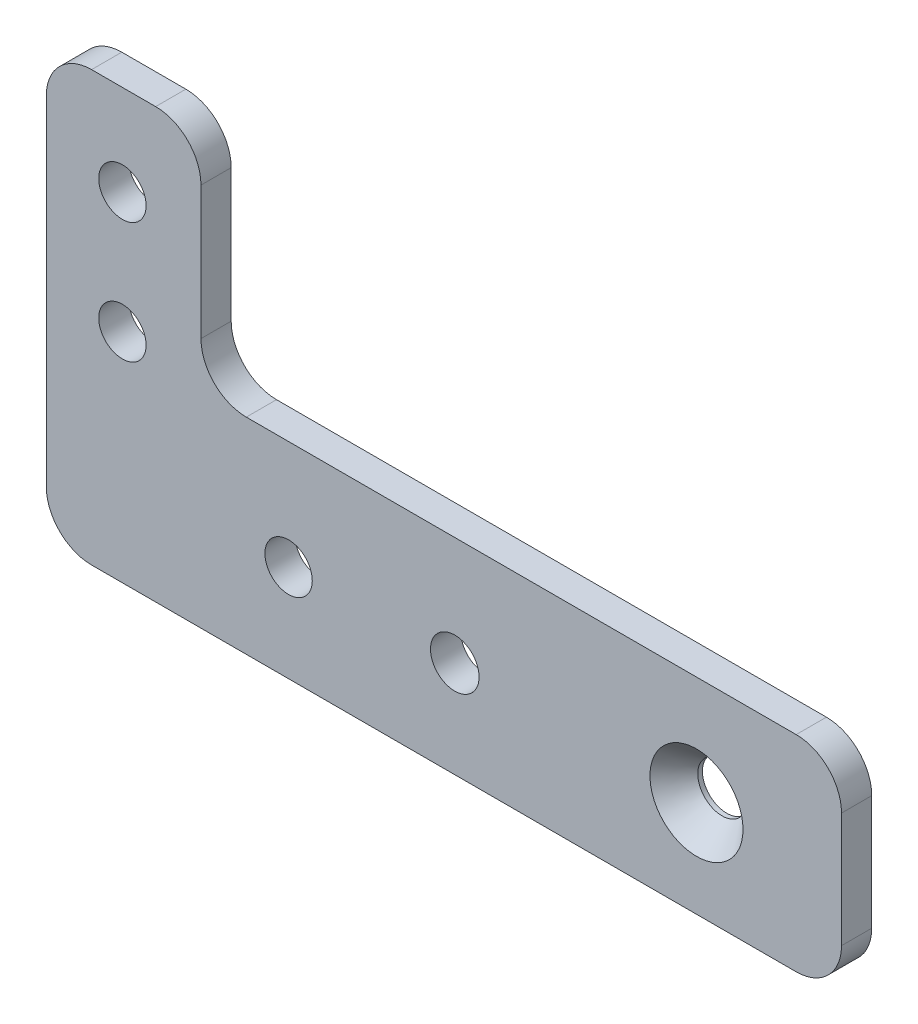
SolidWorks part; units mm, degrees
material "6061-T6 (SS)"
ref_plane "Front Plane" through (0, 0, 0) normal (0, 0, 1) x (1, 0, 0)
ref_plane "Top Plane" through (0, 0, 0) normal (0, 1, 0) x (1, 0, 0)
ref_plane "Right Plane" through (0, 0, 0) normal (1, 0, 0) x (0, 0, -1)
sketch "Sketch1" plane through (0, 0, 0) normal (0, 0, 1) x (1, 0, 0)
  line L0 (-21.59, 23.8125) -> (-37.846, 23.8125) construction
  line L1 (-45.72, -23.8125) -> (45.72, -23.8125)
  line L2 (-45.72, -23.8125) -> (-45.72, 23.8125)
  line L3 (-45.72, 23.8125) -> (45.72, 23.8125)
  line L4 (45.72, -23.8125) -> (45.72, 23.8125)
  line L5 (-45.72, -23.8125) -> (45.72, 23.8125) construction
  line L6 (-45.72, 23.8125) -> (45.72, -23.8125) construction
  line L7 (45.72, 23.8125) -> (-21.59, 23.8125)
  line L8 (45.72, 23.8125) -> (45.72, 0.3175)
  line L9 (45.72, 0.3175) -> (-21.59, 0.3175)
  line L10 (-21.59, 23.8125) -> (-21.59, 0.3175)
  line L11 (-45.72, -23.8125) -> (-37.846, -23.8125)
  line L12 (-45.72, -23.8125) -> (-45.72, 23.8125)
  line L13 (-45.72, 23.8125) -> (-37.846, 23.8125)
  line L14 (-37.846, -23.8125) -> (-37.846, 23.8125)
  line L15 (-37.846, -23.8125) -> (45.72, -23.8125)
  line L16 (-37.846, -23.8125) -> (-37.846, -21.2725)
  line L17 (-37.846, -21.2725) -> (45.72, -21.2725)
  line L18 (45.72, -23.8125) -> (45.72, -21.2725)
  line L19 (-21.59, 23.8125) -> (-37.846, 23.8125) construction
  line L20 (-29.845, 23.8125) -> (-29.845, -21.2725) construction
  circle A0 centre (-29.845, -11.1125) radius 2.4892
  circle A1 centre (-29.845, 1.5875) radius 2.4892
  circle A2 centre (-29.845, 14.2875) radius 2.4892
  circle A4 centre (-12.3825, -11.1125) radius 2.4892
  circle A5 centre (5.08, -11.1125) radius 2.5527
  circle A7 centre (30.48, -11.1125) radius 2.5527
  point P0 (0, 0)
  dimension "D7" = 17.4625
  dimension "D18" = 5.1054
  dimension "D19" = 4.9784
  dimension "D13" = 25.4
  dimension "D8" = 50.8
  dimension "D1" = 91.44
  dimension "D2" = 9.525
  dimension "D3" = 24.13
  dimension "D4" = 24.13
  dimension "D5" = 7.874
  dimension "D6" = 47.625
  dimension "D9" = 12.7
  dimension "D10" = 12.7
  dimension "D11" = 12.7
  dimension "D12" = 15.875
  dimension "D16" = 2.54
extrude "Boss-Extrude1" add sketch "Sketch1" along normal blind 3.175 contours L14 L17 L4 L9 L10 L3 A5 A4 A2 A1 A0 | A0 region at (-1.447, -6.6351, 0) region at (-29.845, -11.1125, 0)
fillet "Fillet1" radius 4.7625 6 edges at (-37.846, 23.8125, 1.5875) (-21.59, 23.8125, 1.5875) (-21.59, 0.3175, 1.5875) (45.72, 0.3175, 1.5875) (45.72, -21.2725, 1.5875) (-37.846, -21.2725, 1.5875)
hole_wizard "CSK for #10 Flat Head Machine Screw1" positions "Sketch3" profile "Sketch4" countersink size "#10" standard "ANSI Inch"
sketch "Sketch3" plane through (0, 0, 3.175) normal (0, 0, 1) x (1, 0, 0)
  point P0 (30.48, -11.1125)
sketch "Sketch4" plane through (30.48, -11.1125, 3.175) normal (1, 0, 0) x (0, -1, 0)
  line L0 (0, 0) -> (0, 20.5838)
  line L1 (0, 20.5838) -> (2.5527, 19.05)
  line L2 (2.5527, 19.05) -> (2.5527, 2.6882)
  line L3 (2.5527, 2.6882) -> (4.8895, 0)
  line L5 (4.8895, 0) -> (0, 0)
  line L6 (-2.5527, 2.6882) -> (-4.8895, 0) construction
  line L10 (0, 20.5838) -> (-2.5527, 19.05) construction
  line L11 (0, -6.35) -> (0, 107.95) construction
  dimension "Hole Dia." = 5.1054
  dimension "Hole Depth" = 19.05
  dimension "Near C'Sink Dia." = 9.779
  dimension "Near C'Sink Angle" = 82
  dimension "Drill Angle" = 118
